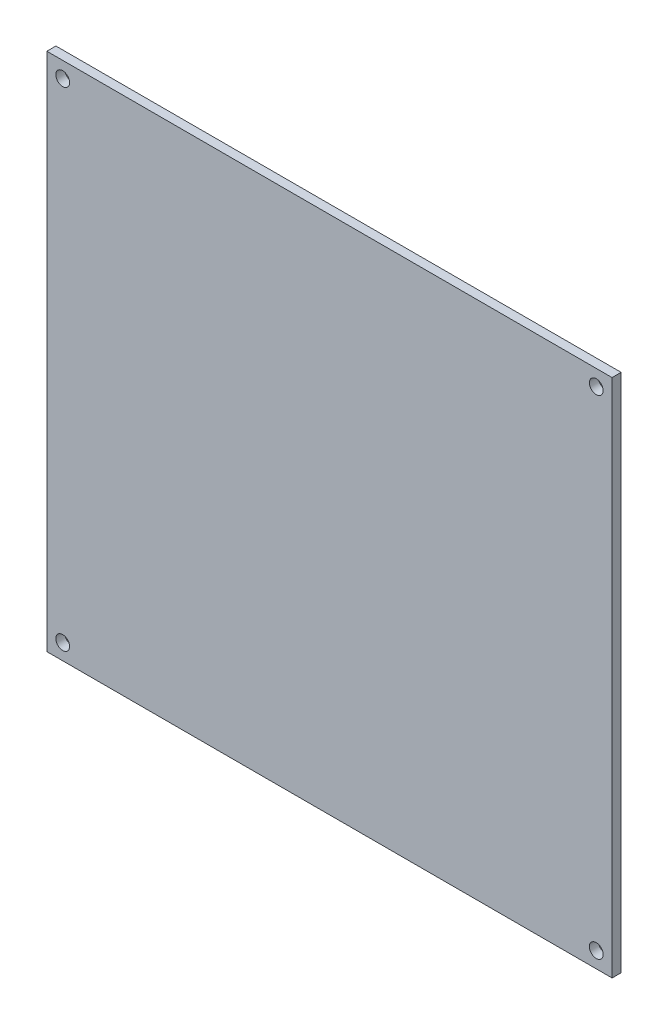
SolidWorks part; units mm, degrees
ref_plane "Front Plane" through (0, 0, 0) normal (0, 0, 1) x (1, 0, 0)
ref_plane "Top Plane" through (0, 0, 0) normal (0, 1, 0) x (1, 0, 0)
ref_plane "Right Plane" through (0, 0, 0) normal (1, 0, 0) x (0, 0, -1)
sketch "Sketch1" plane through (0, 0, 0) normal (0, 1, 0) x (1, 0, 0)
  line L1 (-62.5, -45) -> (62.5, -45)
  line L2 (-62.5, -45) -> (-62.5, 45)
  line L3 (-62.5, 45) -> (62.5, 45)
  line L4 (62.5, -45) -> (62.5, 45)
  line L5 (-62.5, -45) -> (62.5, 45) construction
  line L6 (-62.5, 45) -> (62.5, -45) construction
  point P0 (0, 0)
  dimension "D1" = 125
  dimension "D2" = 90
extrude "Boss-Extrude1" add sketch "Sketch1" along normal blind 115
shell "Shell1" thickness 2
sketch "Sketch4" plane through (0, 113, 0) normal (0, -1, 0) x (1, 0, 0)
  line L1 (-60.5, -43) -> (7.3, -43)
  line L2 (-60.5, -43) -> (-60.5, -26.3)
  line L3 (-60.5, -26.3) -> (7.3, -26.3)
  line L4 (7.3, -43) -> (7.3, -26.3)
  dimension "D1" = 67.8
  dimension "D2" = 16.7
extrude "Cut-Extrude1" cut sketch "Sketch4" against normal blind 1
sketch "Sketch5" plane through (0, 114, 0) normal (0, -1, 0) x (1, 0, 0)
  line L0 (-60.5, -34.65) -> (-50.5, -34.65)
  line L1 (-60.5, -26.3) -> (-60.5, -43) construction
  circle A0 centre (-50.5, -34.65) radius 3.25
  dimension "D1" = 10
extrude "Cut-Extrude2" cut sketch "Sketch5" against normal blind 37
sketch "Sketch6" plane through (0, 0, -43) normal (0, 0, 1) x (1, 0, 0)
  line L0 (7.3, 113) -> (7.3, 2)
  line L1 (-60.5, 2) -> (60.5, 2) construction
  line L3 (7.3, 113) -> (8.3, 113)
  line L4 (7.3, 113) -> (7.3, 2)
  line L5 (7.3, 2) -> (8.3, 2)
  line L6 (8.3, 113) -> (8.3, 2)
  line M2 (-60.5, 2) -> (60.5, 2)
  line M4 (60.5, 113) -> (7.3, 113)
  dimension "D1" = 1
extrude "Boss-Extrude2" add sketch "Sketch6" along normal blind 10 contours L6 L0 M4 M2
fillet "Fillet1" radius 10 1 edges at (8.3, 57.5, -43)
fillet "Fillet2" radius 1 1 edges
sketch "Sketch7" plane through (62.5, 0, 0) normal (1, 0, 0) x (0, 0, -1)
  line L0 (0, 0) -> (0, 35)
  line L1 (-45, 0) -> (45, 0) construction
  circle A1 centre (0, 35) radius 13
  dimension "D1" = 35
extrude "Cut-Extrude3" cut sketch "Sketch7" against normal blind 10
sketch "Sketch8" plane through (-62.5, 0, 0) normal (-1, 0, 0) x (0, 0, 1)
  line L0 (-45, 115) -> (3, 115)
  line L1 (-45, 115) -> (45, 115) construction
  line L2 (45, 115) -> (45, 0) construction
  line L3 (3, 115) -> (27, 115)
  line L4 (3, 115) -> (3, 65.9585)
  line L5 (3, 65.9585) -> (27, 65.9585)
  line L6 (27, 115) -> (27, 65.9585)
  line M7 (45, 115) -> (-45, 115)
  dimension "D1" = 24
  dimension "D2" = 18
extrude "Boss-Extrude3" add sketch "Sketch8" along normal blind 12 contours L6 L4 L5 M7
chamfer "Chamfer1" distance 10 angle 50 1 edges at (-62.5, 90.4793, 3)
sketch "Sketch9" plane through (0, 115, 0) normal (0, 1, 0) x (1, 0, 0)
  line L0 (-74.5, -21.3932) -> (-72.5, -21.3932)
  line L1 (-74.5, -27) -> (-74.5, -3) construction
  line L2 (-72.5, -21.3932) -> (-72.5, -25)
  line L3 (-72.5, -25) -> (-64.1397, -25)
  line L4 (-64.1397, -25) -> (-64.1397, -5)
  line L5 (-64.1397, -5) -> (-72.5, -5)
  line L6 (-72.5, -5) -> (-72.5, -21.3932)
  line L7 (-74.5, -27) -> (-62.5, -27) construction
  line L9 (-74.5, -3) -> (-74.4175, -3) construction
  dimension "D1" = 2
  dimension "D2" = 2
  dimension "D3" = 2
extrude "Cut-Extrude4" cut sketch "Sketch9" against normal blind 40 contours L5 L6 L2 L3 L4
sketch "Sketch10" plane through (0, 0, -43) normal (0, 0, 1) x (1, 0, 0)
  line L0 (-35.9, 113) -> (60.5, 113)
  line L4 (19.3, 113) -> (54.3, 113)
  line L5 (19.3, 113) -> (19.3, 75.5)
  line L6 (19.3, 75.5) -> (54.3, 75.5)
  line L7 (54.3, 113) -> (54.3, 75.5)
  line L10 (19.3, 110.5) -> (54.3, 110.5)
  line L11 (12.3, 113) -> (12.3, 2) construction
  line L12 (36.8, 75.5) -> (36.8, 91.75)
  line L13 (19.3, 94.25) -> (31.5357, 94.25)
  line L14 (22.3, 75.5) -> (22.3, 78.5)
  line L15 (19.3, 91.75) -> (26.0315, 91.75)
  circle A0 centre (22.3, 78.5) radius 1.4
  circle A1 centre (51.3, 78.5) radius 1.4
  circle A2 centre (51.3, 105) radius 1.4
  circle A3 centre (22.3, 105) radius 1.4
  point P4 (12.3, 113)
  point P29 (0, 0)
  dimension "D5" = 3
  dimension "D7" = 2.5
  dimension "D1" = 7
  dimension "D2" = 2.5
  dimension "D3" = 35
  dimension "D4" = 35
  dimension "D6" = 3
extrude "Boss-Extrude4" add sketch "Sketch10" along normal blind 10 contours A3 | A2 | A1 | A0
fillet "Fillet3" radius 1 4 edges at (23.7, 105, -43) (52.7, 105, -43) (52.7, 78.5, -43) (23.7, 78.5, -43)
sketch "Sketch11" plane through (0, 113, 0) normal (0, -1, 0) x (1, 0, 0)
  line L0 (51.3, -42) -> (42.3, -42)
  line L1 (52.7, -42) -> (49.9, -42) construction
  line L2 (42.3, -42) -> (42.3, -38.5)
  line L3 (42.3, -42) -> (42.3, -43)
  line L4 (60.5, -43) -> (12.3, -43) construction
  line L5 (42.3, -43) -> (42.3, -42)
  circle A0 centre (42.3, -38.5) radius 3.25
  dimension "D1" = 9
  dimension "D2" = 3.5
extrude "Cut-Extrude5" cut sketch "Sketch11" against normal blind 161
sketch "Sketch13" plane through (-60.5, 0, 0) normal (1, 0, 0) x (0, 0, -1)
  line L0 (18, 0) -> (18, 25)
  line L2 (43, 114) -> (43, 2) construction
  circle A0 centre (18, 25) radius 5.75
  dimension "D1" = 25
  dimension "D2" = 25
extrude "Cut-Extrude6" cut sketch "Sketch13" against normal blind 161
sketch "Sketch14" plane through (0, 0, 0) normal (0, -1, 0) x (1, 0, 0)
  line L0 (0, 45) -> (0, 34.9919)
  line L1 (-62.5, 45) -> (62.5, 45) construction
  line L2 (0, -49.5) -> (0, 49.5) construction
  line L3 (-62.5, 0) -> (-42.0329, 0)
  line L4 (-62.5, -45) -> (-62.5, 45) construction
  line L5 (63.25, 0) -> (-63.25, 0) construction
  line L6 (-55.5, 45) -> (-55.5, 38)
  circle A0 centre (-55.5, 38) radius 5.5
  circle A1 centre (-55.5, -38) radius 5.5
  circle A2 centre (55.5, -38) radius 5.5
  circle A3 centre (55.5, 38) radius 5.5
  circle A4 centre (-55.5, 38) radius 6
  circle A5 centre (55.5, 38) radius 6
  circle A6 centre (55.5, -38) radius 6
  circle A7 centre (-55.5, -38) radius 6
  dimension "D1" = 7
  dimension "D2" = 7
extrude "Boss-Extrude5" add sketch "Sketch14" along normal blind 1 contours A6 A2 | A5 A3 | A4 | A7 | A0
fillet "Fillet4" radius 0.5 2 edges at (-55.5, 0, 32) (-55.5, -1, 32)
fillet "Fillet5" radius 0.5 6 edges at (55.5, 0, 32) (55.5, -1, 32) (55.5, 0, -44) (55.5, -1, -44) (-55.5, 0, -44) (-55.5, -1, -44)
sketch "Sketch17" plane through (0, 115, 0) normal (0, 1, 0) x (1, 0, 0)
  line L0 (22.5, -45) -> (22.5, -35)
  line L1 (-62.5, -45) -> (62.5, -45) construction
  line L2 (22.5, -35) -> (62.5, -35)
  line L3 (62.5, -45) -> (62.5, 45) construction
  circle A0 centre (22.5, -35) radius 2.5
  circle A1 centre (29.5, -35) radius 2.5
  circle A2 centre (36.5, -35) radius 2.5
  circle A3 centre (43.5, -35) radius 2.5
  dimension "D1" = 10
  dimension "D2" = 40
  dimension "D3" = 7
  dimension "D4" = 7
  dimension "D5" = 7
extrude "Cut-Extrude7" cut sketch "Sketch17" against normal blind 9 contours L0 A0 L2 | L2 A0 L0 | L2 A1 | L2 A1 | L2 A2 | L2 A2 | L2 A3 | L2 A3
sketch "Sketch18" plane through (0, 0, 45) normal (0, 0, 1) x (1, 0, 0)
  line L0 (-60.5, 103) -> (-50.5, 112.9881)
  line L1 (-60.5, 114) -> (-60.5, 2) construction
  line L2 (-50.5, 112.9881) -> (-60.5, 113)
  line L3 (-60.5, 103) -> (-60.5, 113)
  line L4 (-60.5, 113) -> (60.5, 113) construction
  line L5 (60.5, 113) -> (60.5, 2) construction
  line L6 (60.5, 57.5) -> (39.7821, 57.5)
  line L7 (0, 113) -> (0, 99.9846)
  line L8 (0, -49.5) -> (0, 49.5) construction
  line L9 (60.5, 103) -> (60.5, 113)
  line L10 (50.5, 112.9881) -> (60.5, 113)
  line L11 (60.5, 103) -> (50.5, 112.9881)
  line L12 (-60.5, 2) -> (-60.5, 12)
  line L13 (-60.5, 12) -> (-50.5, 2)
  line L14 (-60.5, 2) -> (60.5, 2) construction
  line L15 (-50.5, 2) -> (-60.5, 2)
  line L16 (50.5, 2) -> (60.5, 12)
  line L17 (60.5, 12) -> (60.5, 2)
  line L18 (60.5, 2) -> (50.5, 2)
  line M14 (60.5, 2) -> (-60.5, 2)
  line M15 (-60.5, 2) -> (-60.5, 113)
  line M17 (60.5, 113) -> (60.5, 2)
  dimension "D1" = 10
  dimension "D2" = 10
  dimension "D3" = 10
  dimension "D4" = 10
  dimension "D5" = 10
  dimension "D6" = 10
extrude "Boss-Extrude6" add sketch "Sketch18" against normal blind 20 contours L13 M15 M14 | L0 L2 M15 | L11 L10 M17 | L16 M14 M17
chamfer "Chamfer2" distance 10 angle 44 2 edges at (55.5, 2, 25) (-55.5, 2, 25)
chamfer "Chamfer3" distance 5 angle 63 2 edges at (60.5, 108, 25) (-60.5, 108, 25)
sketch "Sketch19" plane through (0, 0, 45) normal (0, 0, 1) x (1, 0, 0)
  line L0 (-62.5, 0) -> (-55.5, 7)
  line L1 (49.5, 0) -> (-49.5, 0) construction
  line L2 (-62.5, 115) -> (-62.5, 0) construction
  line L3 (-60.5, 12) -> (-50.5, 2) construction
  line L4 (0, 113) -> (0, 101.4841)
  line L5 (-60.5, 113) -> (60.5, 113) construction
  line L6 (0, -49.5) -> (0, 49.5) construction
  line L7 (-60.5, 57.5) -> (-50.0454, 57.5)
  line L8 (-60.5, 103) -> (-60.5, 12) construction
  circle A0 centre (-59, 3.5) radius 1.525
  circle A1 centre (-59, 111.5) radius 1.525
  circle A2 centre (59, 111.5) radius 1.525
  circle A3 centre (59, 3.5) radius 1.525
  line M7 (-50.5, 112.9881) -> (-60.5, 113)
extrude "Cut-Extrude8" cut sketch "Sketch19" against normal blind 18 contours A1 M7 | A3 | L0 A0 | L0 A0 | A2
sketch "Sketch20" plane through (0, 0, 45) normal (0, 0, 1) x (1, 0, 0)
  line L0 (-62.5, 0) -> (62.5, 0)
  line L1 (62.5, 0) -> (62.5, 115)
  line L2 (62.5, 115) -> (-62.5, 115)
  line L3 (-62.5, 115) -> (-62.5, 0)
  line L8 (-62.5, 0) -> (62.5, 0)
  line L9 (62.5, 0) -> (62.5, 115)
  line L10 (62.5, 115) -> (-62.5, 115)
  line L11 (-62.5, 115) -> (-62.5, 0)
  line L12 (-62.5, 0) -> (62.5, 0)
  line L13 (62.5, 0) -> (62.5, 115)
  line L14 (62.5, 115) -> (-62.5, 115)
  line L15 (-62.5, 115) -> (-62.5, 0)
  dimension "D1" = 0
  dimension "D2" = 0
sketch "Sketch22" plane through (0, 0, 45) normal (0, 0, 1) x (1, 0, 0)
  line L8 (-62.5, 0) -> (62.5, 0)
  line L9 (62.5, 0) -> (62.5, 115)
  line L10 (62.5, 115) -> (-62.5, 115)
  line L11 (-62.5, 115) -> (-62.5, 0)
  line L12 (-62.5, 0) -> (62.5, 0)
  line L13 (62.5, 0) -> (62.5, 115)
  line L14 (62.5, 115) -> (-62.5, 115)
  line L15 (-62.5, 115) -> (-62.5, 0)
  dimension "D1" = 0
sketch "Sketch23" plane through (62.5, 0, 0) normal (1, 0, 0) x (0, 0, -1)
  line L0 (-45, 115) -> (45, 115) construction
  line L1 (-44, 115) -> (59.2718, 115)
  line L2 (-44, 115) -> (-44, -14.7912)
  line L3 (-44, -14.7912) -> (59.2718, -14.7912)
  line L4 (59.2718, 115) -> (59.2718, -14.7912)
  line L6 (-45, 115) -> (-45, 0) construction
  dimension "D1" = 1
extrude "Cut-Extrude9" cut sketch "Sketch23" against normal blind 210 contours L2 L1 L4 L3
sketch "Sketch24" plane through (0, 0, 45) normal (0, 0, 1) x (1, 0, 0)
  line L1 (-62.5, 0) -> (62.5, 0)
  line L2 (-62.5, 0) -> (-62.5, 115)
  line L3 (-62.5, 115) -> (62.5, 115)
  line L4 (62.5, 0) -> (62.5, 115)
extrude "Boss-Extrude10" add sketch "Sketch24" along normal blind 1
sketch "Sketch25" plane through (0, 0, 44) normal (0, 0, -1) x (-1, 0, 0)
  circle A22 centre (-59, 111.5) radius 1.525
  circle A23 centre (59, 111.5) radius 1.525
  circle A24 centre (59, 3.5) radius 1.525
  circle A25 centre (-59, 3.5) radius 1.525
  circle M1 centre (-59, 3.5) radius 1.525
  circle M2 centre (59, 3.5) radius 1.525
  arc M7 (-58.7137, 112.9979) -> (-59.2828, 112.9986) centre (-59, 111.5) cw
  arc M10 (-59.275, 113) -> (-58.725, 113) centre (-59, 111.5) cw
extrude "Cut-Extrude10" cut sketch "Sketch25" against normal blind 2 contours A22 M10 M7 | M1 | M2 | A23
